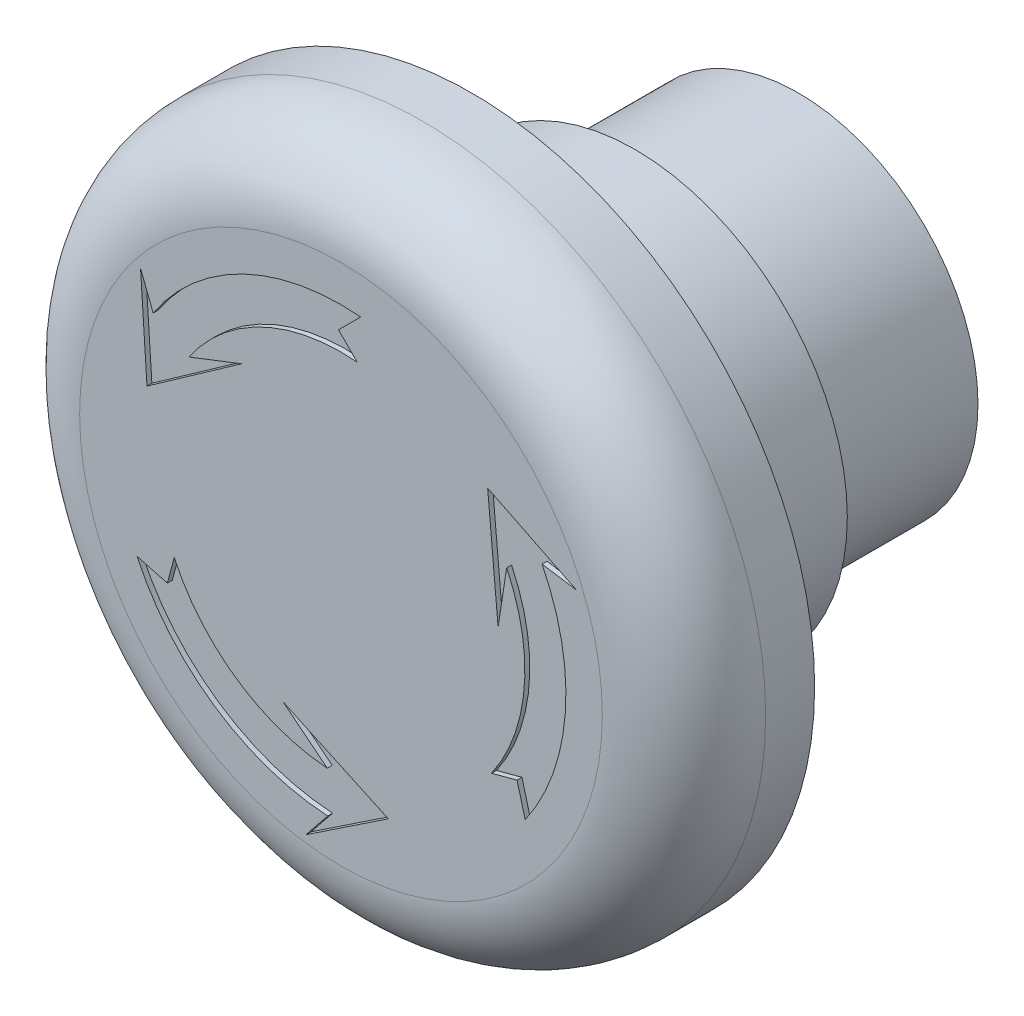
SolidWorks part; units mm, degrees
material "SKD11淬火HRC56－60"
ref_plane "前基準面" through (0, 0, 0) normal (0, 0, 1) x (1, 0, 0)
ref_plane "上基準面" through (0, 0, 0) normal (0, 1, 0) x (1, 0, 0)
ref_plane "右基準面" through (0, 0, 0) normal (1, 0, 0) x (0, 0, -1)
sketch "草图1" plane through (0, 0, 0) normal (0, 0, 1) x (1, 0, 0)
  circle A0 centre (0, 0) radius 11
  dimension "D1" = 22
extrude "凸台-拉伸1" add sketch "草图1" along normal blind 10
sketch "草图2" plane through (0, 0, 10) normal (0, 0, 1) x (1, 0, 0)
  circle A0 centre (0, 0) radius 13
  dimension "D1" = 26
extrude "凸台-拉伸2" add sketch "草图2" along normal blind 10
sketch "草图6" plane through (0, 0, 20) normal (0, 0, 1) x (1, 0, 0)
  circle A0 centre (0, 0) radius 21
  dimension "D1" = 42
extrude "凸台-拉伸5" add sketch "草图6" along normal blind 8
fillet "圆角4" radius 5 1 edges at (21, 0, 28)
sketch "草图7" plane through (0, 0, 28) normal (0, 0, 1) x (1, 0, 0)
  line L0 (-9.305, 6.3404) -> (-6.0902, 7.5908)
  line L1 (-6.0902, 7.5908) -> (-11.8771, 3.5127)
  line L2 (-11.8771, 3.5127) -> (-12.2713, 9.5609)
  line L3 (-12.2713, 9.5609) -> (-11.4997, 7.577)
  line L4 (1.2058, 13.7186) -> (-0.1517, 12.3611)
  line L5 (-0.1517, 12.3611) -> (0.9934, 11.2159)
  arc A0 (0.9934, 11.2159) -> (-9.305, 6.3404) centre (0, 0) ccw
  arc A1 (1.2058, 13.7186) -> (-11.4997, 7.577) centre (0, 0) ccw
extrude "切除-拉伸3" cut sketch "草图7" against normal blind 0.3
ref_axis "基准轴1" through (0, 0, 20) along (0, 0, -1)
pattern_circular "阵列(圆周)1" count 3 over 360 about axis through (0, 0, 20) along (0, 0, -1) of "切除-拉伸3"
